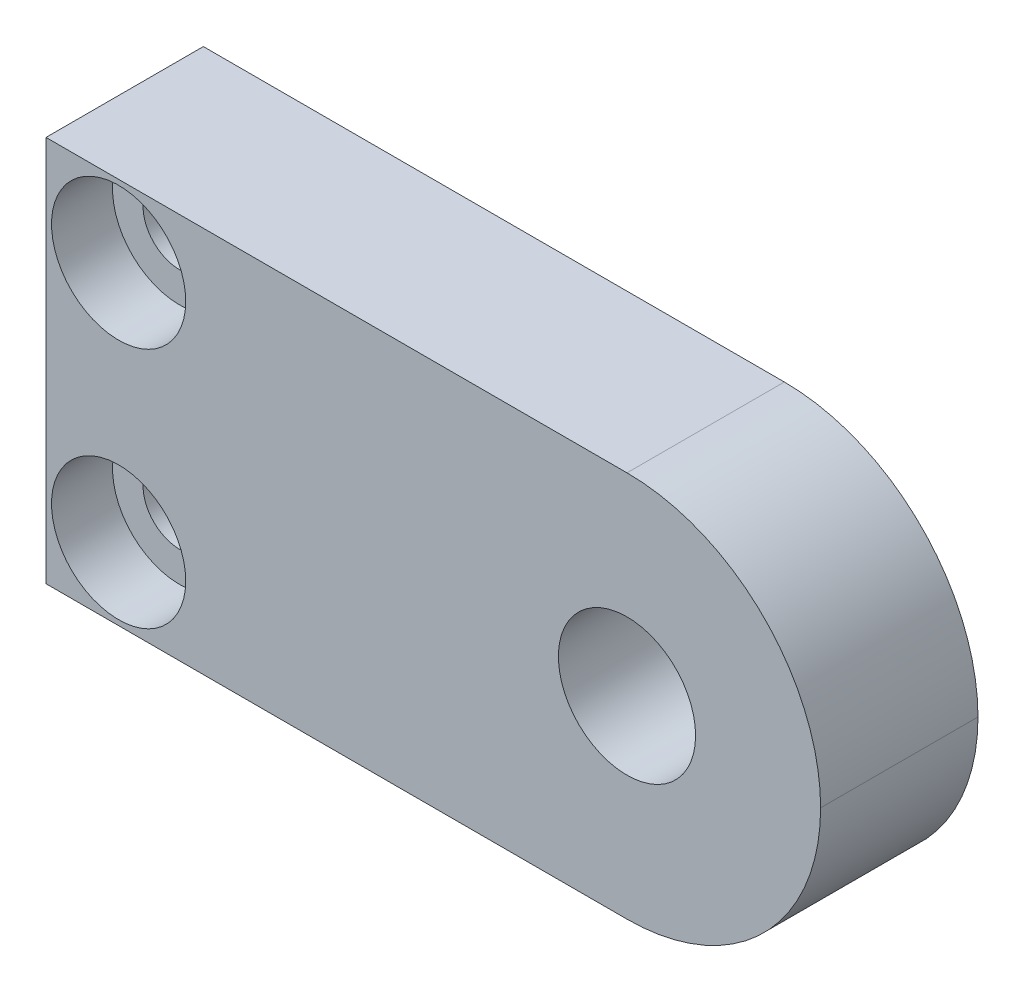
SolidWorks part; units mm, degrees
material "6061-T6 (SS)"
ref_plane "Front Plane" through (0, 0, 0) normal (0, 0, 1) x (1, 0, 0)
ref_plane "Top Plane" through (0, 0, 0) normal (0, 1, 0) x (1, 0, 0)
ref_plane "Right Plane" through (0, 0, 0) normal (1, 0, 0) x (0, 0, -1)
sketch "Sketch1" plane through (0, 0, 0) normal (0, 0, 1) x (1, 0, 0)
  line L0 (0, -2.8377) -> (0, 2.8377) construction
  line L1 (0, 6.3373) -> (25.4, 6.3373)
  line L2 (0, 6.3373) -> (0, -6.3373)
  line L3 (0, -6.3373) -> (25.4, -6.3373)
  line L4 (25.4, 6.3373) -> (25.4, -6.3373)
  line L5 (2.8377, 0) -> (-2.8377, 0) construction
  point P6 (0, 0)
  dimension "D1" = 12.6746
  dimension "D2" = 25.4
extrude "Boss-Extrude1" add sketch "Sketch1" along normal blind 5.1594
sketch "Sketch2" plane through (0, 0, 5.1594) normal (0, 0, 1) x (1, 0, 0)
  line L0 (0, -2.8377) -> (0, 2.8377) construction
  line L2 (2.8377, 0) -> (-2.8377, 0) construction
  circle A0 centre (19.05, 0) radius 2.2492
  dimension "D1" = 19.05
  dimension "D3" = 4.4983
extrude "Cut-Extrude1" cut sketch "Sketch2" against normal through all
fillet "Fillet1" radius 6.35 2 edges at (25.4, -6.3373, 2.5797) (25.4, 6.3373, 2.5797)
hole_wizard "CBORE for M2 SHCS1" positions "Sketch3" profile "Sketch4" counterbore size "M2" standard "ANSI Metric" end condition up to next
sketch "Sketch3" plane through (0, 0, 5.1594) normal (0, 0, 1) x (1, 0, 0)
  line L0 (0, -2.8377) -> (0, 2.8377) construction
  line L1 (2.8377, 0) -> (-2.8377, 0) construction
  point P0 (2.3813, 3.9688)
  point P2 (2.3813, -3.9688)
  dimension "D1" = 2.3813
  dimension "D2" = 3.9688
  dimension "D3" = 7.9375
sketch "Sketch4" plane through (2.3813, 3.9688, 5.1594) normal (1, 0, 0) x (0, -1, 0)
  line L0 (0, 0) -> (0, 5.1594)
  line L1 (0, 5.1594) -> (1.2, 5.1594)
  line L3 (1.2, 5.1594) -> (1.2, 2)
  line L4 (1.2, 2) -> (2.2, 2)
  line L5 (2.2, 2) -> (2.2, 0)
  line L7 (2.2, 0) -> (0, 0)
  line L11 (0, -6.35) -> (0, 107.95) construction
  dimension "Thru Hole Dia." = 2.4
  dimension "Thru Hole Depth" = 5.1594
  dimension "C'Bore Dia." = 4.4
  dimension "C'Bore Depth" = 2
